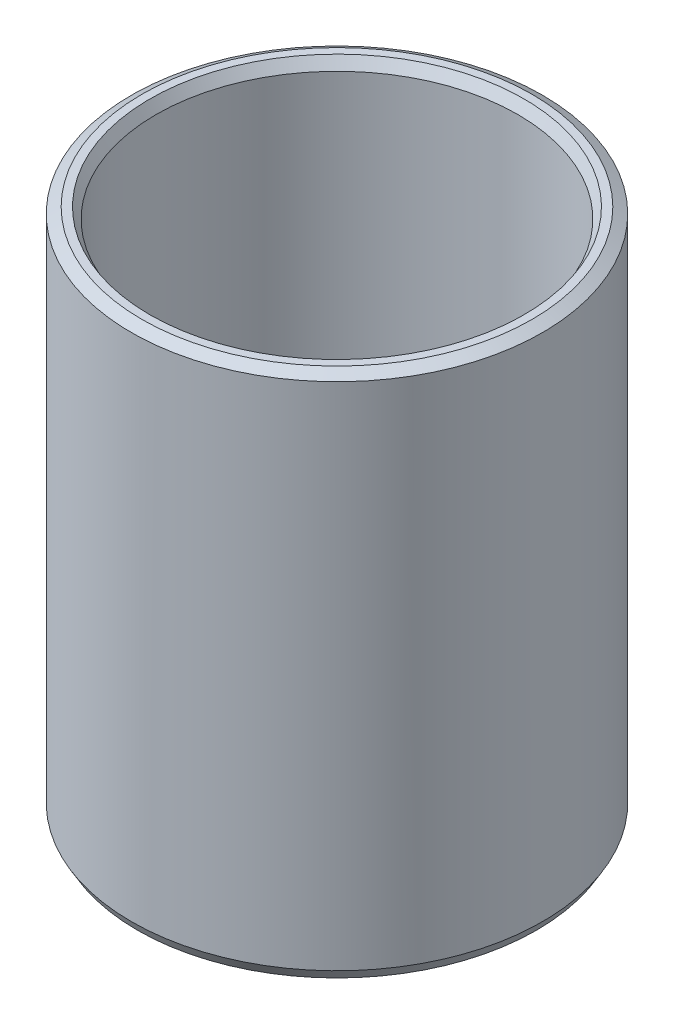
SolidWorks part; units mm, degrees
ref_plane "Front Plane" through (0, 0, 0) normal (0, 0, 1) x (1, 0, 0)
ref_plane "Top Plane" through (0, 0, 0) normal (0, 1, 0) x (1, 0, 0)
ref_plane "Right Plane" through (0, 0, 0) normal (1, 0, 0) x (0, 0, -1)
sketch "Sketch1" plane through (0, 0, 0) normal (0, 1, 0) x (1, 0, 0)
  circle A0 centre (0, 0) radius 42.5
  dimension "SLEEVE_OD" = 85
extrude "Boss-Extrude1" add sketch "Sketch1" along normal blind 108.8908
sketch "Sketch2" plane through (0, 0, 0) normal (0, 1, 0) x (1, 0, 0)
  circle A0 centre (0, 0) radius 37.4052
  dimension "BORE_D" = 74.8104
extrude "Cut-Extrude1" cut sketch "Sketch2" along normal through all
chamfer "Chamfer1" distance 1.2584 angle 60 4 edges at (0, 108.8908, 37.4052) (0, 0, 37.4052) (0, 0, 42.5) (0, 108.8908, 42.5) first distance on face at (0, 108.8908, 37.4052) first distance on face at (0, 0, 37.4052) first distance on face at (0, 108.8908, 42.5)
